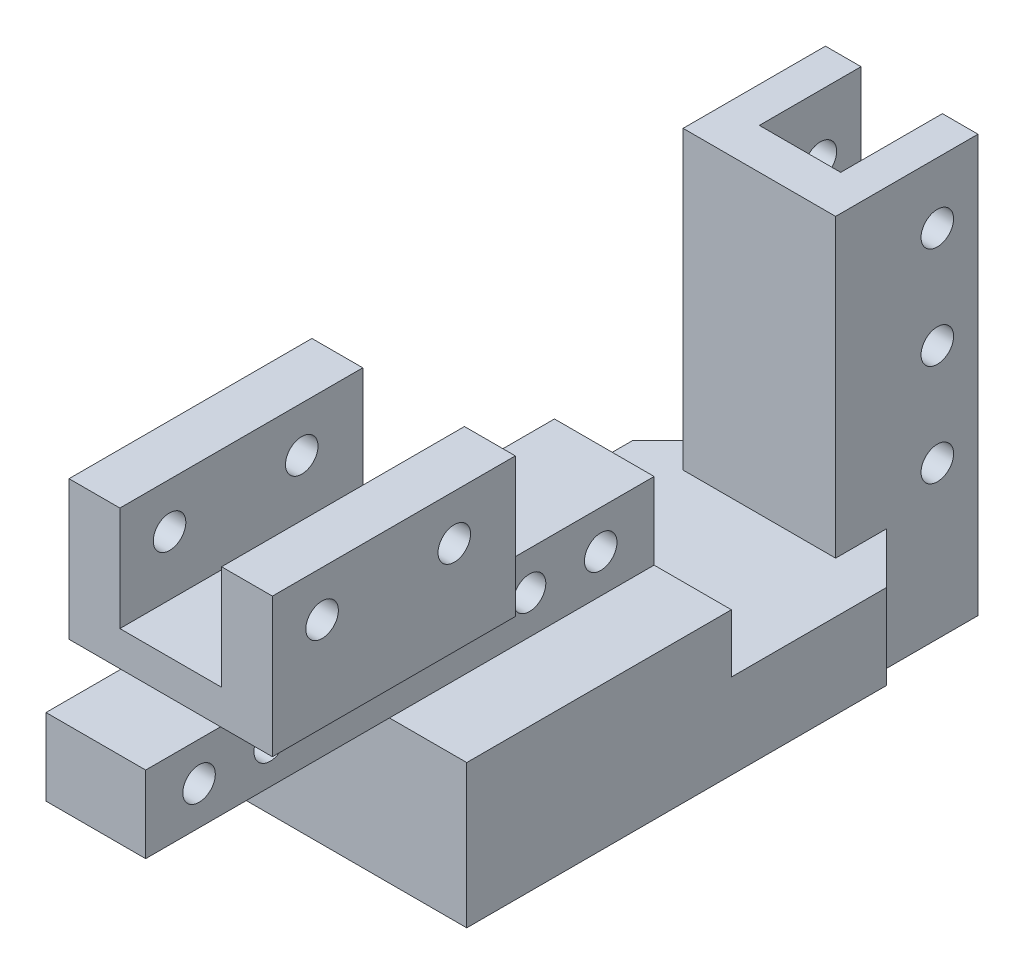
SolidWorks part; units mm, degrees
ref_plane "前视基准面" through (0, 0, 0) normal (0, 0, 1) x (1, 0, 0)
ref_plane "上视基准面" through (0, 0, 0) normal (0, 1, 0) x (1, 0, 0)
ref_plane "右视基准面" through (0, 0, 0) normal (1, 0, 0) x (0, 0, -1)
sketch "草图2" plane through (0, 0, 0) normal (1, 0, 0) x (0, 0, -1)
  line L0 (7, 0) -> (32.5, 0) construction
  line L2 (44.75, 3.775) -> (-5.25, 3.775)
  line L3 (44.75, 3.775) -> (44.75, -3.775)
  line L4 (44.75, -3.775) -> (-5.25, -3.775)
  line L5 (-5.25, 3.775) -> (-5.25, -3.775)
  line L6 (44.75, 3.775) -> (-5.25, -3.775) construction
  line L7 (44.75, -3.775) -> (-5.25, 3.775) construction
  circle A0 centre (0, 0) radius 1.6
  circle A1 centre (7, 0) radius 1.6
  circle A2 centre (32.5, 0) radius 1.6
  circle A3 centre (39.5, 0) radius 1.6
  point P9 (19.75, 0)
  dimension "D1" = 25.5
  dimension "D2" = 7
  dimension "D3" = 3.775
extrude "凸台-拉伸1" add sketch "草图2" along normal mid plane 9.8
sketch "草图3" plane through (0, 0, 0) normal (1, 0, 0) x (0, 0, -1)
  line L0 (7, 13) -> (20, 13) construction
  line L1 (2.1144, 3.775) -> (2.1144, 17.4551)
  line L2 (44.75, 3.775) -> (-5.25, 3.775) construction
  line L3 (2.1144, 17.4551) -> (26, 17.4551)
  line L4 (26, 17.4551) -> (26, 3.775)
  line L5 (26, 3.775) -> (2.1144, 3.775)
  circle A0 centre (7, 13) radius 1.6
  circle A1 centre (20, 13) radius 1.6
  point P0 (7, 0)
  point P6 (13.5, 13)
  dimension "D1" = 13
  dimension "D3" = 3.2
  dimension "D4" = 3.2
  dimension "D2" = 6
extrude "凸台-拉伸2" add sketch "草图3" along normal mid plane 20
sketch "草图4" plane through (0, 0, -2.1144) normal (0, 0, 1) x (1, 0, 0)
  line L0 (10, 17.4551) -> (-10, 17.4551) construction
  line L1 (5, 7.1905) -> (-5, 7.1905)
  line L2 (5, 7.1905) -> (5, 17.4551)
  line L3 (5, 17.4551) -> (-5, 17.4551)
  line L4 (-5, 7.1905) -> (-5, 17.4551)
  line L5 (5, 7.1905) -> (-5, 17.4551) construction
  line L6 (5, 17.4551) -> (-5, 7.1905) construction
  point P0 (0, 12.3228)
extrude "切除-拉伸1" cut sketch "草图4" against normal through all
sketch "草图6" plane through (0, 0, 0) normal (1, 0, 0) x (0, 0, -1)
  line L0 (70, 3.6) -> (70, 13.6) construction
  line L2 (74, -21.4) -> (60, -21.4)
  line L3 (74, -21.4) -> (74, 19.6)
  line L4 (74, 19.6) -> (60, 19.6)
  line L5 (60, -21.4) -> (60, 19.6)
  line L6 (74, -21.4) -> (60, 19.6) construction
  line L7 (74, 19.6) -> (60, -21.4) construction
  circle A0 centre (70, 3.6) radius 1.6
  circle A1 centre (70, 13.6) radius 1.6
  circle A2 centre (70, -6.4) radius 1.6
  point P4 (70, 8.6)
  point P9 (67, -0.9)
  dimension "D1" = 60
  dimension "D6" = 10
  dimension "D2" = 3.6
  dimension "D3" = 10
  dimension "D4" = 4
  dimension "D5" = 14
  dimension "D7" = 6
  dimension "D8" = 15
extrude "凸台-拉伸4" add sketch "草图6" along normal mid plane 15 separate body
sketch "草图7" plane through (0, 0, -74) normal (0, 0, 1) x (1, 0, 0)
  line L0 (7.5, 19.6) -> (-7.5, 19.6) construction
  line L1 (-4, 19.6) -> (4, 19.6)
  line L2 (-4, 19.6) -> (-4, -21.4)
  line L3 (-4, -21.4) -> (4, -21.4)
  line L4 (4, 19.6) -> (4, -21.4)
  line L5 (7.5, -21.4) -> (-7.5, -21.4) construction
extrude "切除-拉伸2" cut sketch "草图7" along normal blind 10
sketch "草图8" plane through (0, 0, 0) normal (1, 0, 0) x (0, 0, -1)
  line L5 (44.75, -3.775) -> (44.75, -9.5061)
  line L10 (44.75, -3.775) -> (44.75, 3.775) construction
  line L11 (44.75, -9.5061) -> (60, -9.5061)
  line L12 (60, 19.6) -> (60, -21.4) construction
  line L13 (60, -9.5061) -> (60, -17.8546)
  line L14 (60, -17.8546) -> (18.7245, -17.8546)
  line L15 (18.7245, -17.8546) -> (18.7245, -3.775)
  line L16 (-5.25, -3.775) -> (44.75, -3.775) construction
  line L17 (18.7245, -3.775) -> (44.75, -3.775)
extrude "凸台-拉伸5" add sketch "草图8" along normal mid plane 25
chamfer "倒角1" distance 5 angle 45 2 edges at (-7.5, -13.6804, -60) (7.5, -13.6804, -60)
